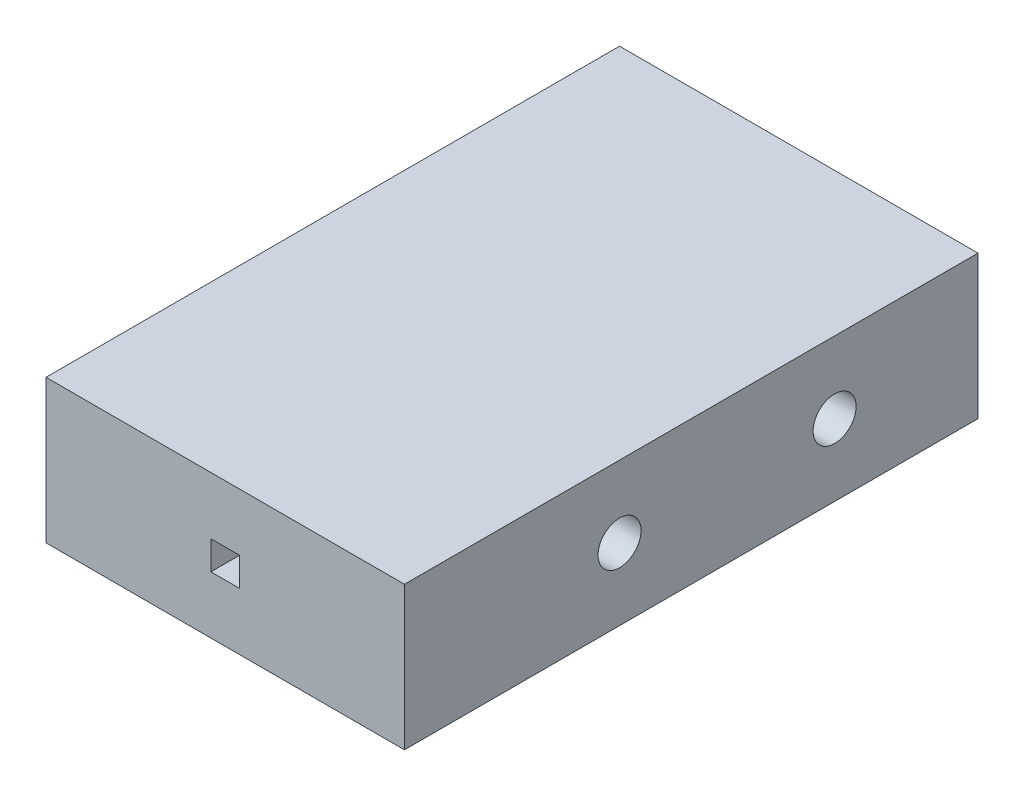
SolidWorks part; units mm, degrees
ref_plane "Plan de face" through (0, 0, 0) normal (0, 0, 1) x (1, 0, 0)
ref_plane "Plan de dessus" through (0, 0, 0) normal (0, 1, 0) x (1, 0, 0)
ref_plane "Plan de droite" through (0, 0, 0) normal (1, 0, 0) x (0, 0, -1)
sketch "Sketch1" plane through (0, 0, 0) normal (0, 1, 0) x (1, 0, 0)
  line L1 (12.5, -20) -> (-12.5, -20)
  line L2 (12.5, -20) -> (12.5, 20)
  line L3 (12.5, 20) -> (-12.5, 20)
  line L4 (-12.5, -20) -> (-12.5, 20)
  line L5 (12.5, -20) -> (-12.5, 20) construction
  line L6 (12.5, 20) -> (-12.5, -20) construction
  point P0 (0, 0)
  dimension "D1" = 25
  dimension "D2" = 40
extrude "Boss-Extrude1" add sketch "Sketch1" along normal blind 10
sketch "Sketch2" plane through (12.5, 0, 0) normal (1, 0, 0) x (0, 0, -1)
  line L0 (20, 10) -> (20, 0) construction
  line L1 (20, 0) -> (-20, 0) construction
  circle A0 centre (10, 5) radius 1.5
  dimension "D1" = 10
  dimension "D2" = 5
extrude "Cut-Extrude1" cut sketch "Sketch2" against normal through all
sketch "Sketch4" plane through (-12.5, 0, 0) normal (-1, 0, 0) x (0, 0, 1)
  line L0 (20, 10) -> (20, 0) construction
  line L1 (-20, 0) -> (20, 0) construction
  circle A0 centre (5, 5) radius 1.5
  point P2 (20, 5)
  dimension "D1" = 15
  dimension "D2" = 5
extrude "Cut-Extrude3" cut sketch "Sketch4" against normal through all
sketch "Sketch6" plane through (0, 0, 20) normal (0, 0, 1) x (1, 0, 0)
  line L0 (-12.5, 10) -> (-12.5, 0) construction
  line L1 (1, 4) -> (-1, 4)
  line L2 (1, 4) -> (1, 6)
  line L3 (1, 6) -> (-1, 6)
  line L4 (-1, 4) -> (-1, 6)
  line L5 (1, 4) -> (-1, 6) construction
  line L6 (1, 6) -> (-1, 4) construction
  point P0 (0, 5)
  dimension "D1" = 2
  dimension "D2" = 2
  dimension "D3" = 12.5
  dimension "D4" = 5
extrude "Cut-Extrude4" cut sketch "Sketch6" against normal through all
